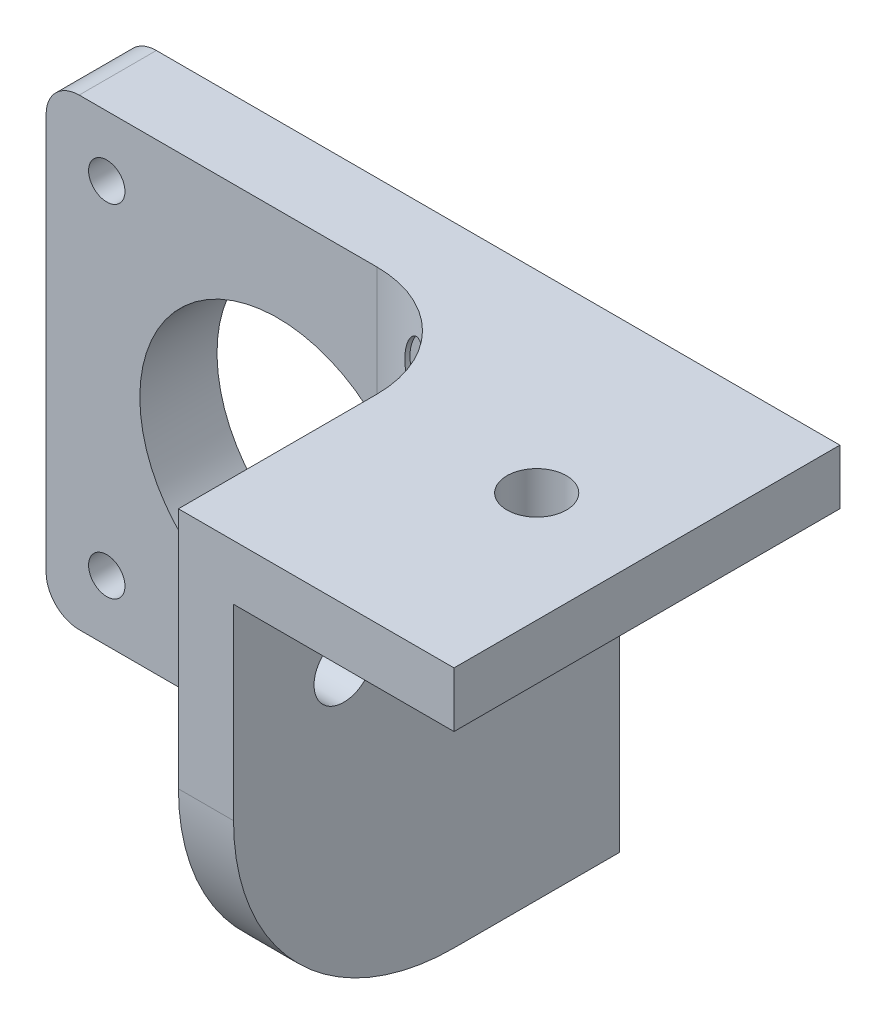
SolidWorks part; units mm, degrees
ref_plane "Front Plane" through (0, 0, 0) normal (0, 0, 1) x (1, 0, 0)
ref_plane "Top Plane" through (0, 0, 0) normal (0, 1, 0) x (1, 0, 0)
ref_plane "Right Plane" through (0, 0, 0) normal (1, 0, 0) x (0, 0, -1)
sketch "Sketch1" plane through (0, 0, 0) normal (0, 0, 1) x (1, 0, 0)
  line L1 (-21, -21) -> (21, -21)
  line L2 (-21, -21) -> (-21, 21)
  line L3 (-21, 21) -> (21, 21)
  line L4 (21, -21) -> (21, 21)
  line L5 (-21, -21) -> (21, 21) construction
  line L6 (-21, 21) -> (21, -21) construction
  point P0 (0, 0)
  dimension "D1" = 42
  dimension "D2" = 42
extrude "Boss-Extrude1" add sketch "Sketch1" along normal blind 7
sketch "Sketch2" plane through (0, 0, 0) normal (0, 0, 1) x (1, 0, 0)
  line L0 (-21, -21) -> (21, -21) construction
  line L1 (19, -21) -> (24, -21)
  line L2 (19, -21) -> (19, 21)
  line L3 (19, 21) -> (24, 21)
  line L4 (24, -21) -> (24, 21)
  line L5 (21, -21) -> (21, 21) construction
  line L6 (21, 21) -> (-21, 21) construction
  dimension "D1" = 3
  dimension "D2" = 5
extrude "Boss-Extrude2" add sketch "Sketch2" along normal blind 35 contours L4 L3 L2 L1
sketch "Sketch3" plane through (0, 0, 7) normal (0, 0, 1) x (1, 0, 0)
  line L1 (-15.5, -15.5) -> (15.5, -15.5) construction
  line L2 (-15.5, -15.5) -> (-15.5, 15.5) construction
  line L3 (-15.5, 15.5) -> (15.5, 15.5) construction
  line L4 (15.5, -15.5) -> (15.5, 15.5) construction
  line L5 (-15.5, -15.5) -> (15.5, 15.5) construction
  line L6 (-15.5, 15.5) -> (15.5, -15.5) construction
  circle A8 centre (-15.5, 15.5) radius 1.65
  circle A9 centre (15.5, 15.5) radius 1.65
  circle A10 centre (15.5, -15.5) radius 1.65
  circle A11 centre (-15.5, -15.5) radius 1.65
  point P0 (0, 0)
  dimension "D1" = 31
  dimension "D2" = 31
  dimension "D3" = 3.3
extrude "Cut-Extrude1" cut sketch "Sketch3" against normal blind 35
sketch "Sketch4" plane through (24, 0, 0) normal (1, 0, 0) x (0, 0, -1)
  line L0 (-35, -21) -> (-35, 21) construction
  line L1 (0, 21) -> (-35, 21)
  line L2 (0, 21) -> (0, 16)
  line L3 (0, 16) -> (-35, 16)
  line L4 (-35, 21) -> (-35, 16)
  dimension "D1" = 5
extrude "Boss-Extrude3" add sketch "Sketch4" along normal blind 20
sketch "Sketch6" plane through (0, 0, 0) normal (0, 0, 1) x (1, 0, 0)
  circle A0 centre (0, 0) radius 12.5
  dimension "D1" = 25
extrude "Cut-Extrude4" cut sketch "Sketch6" along normal blind 20
fillet "Fillet2" radius 10 1 edges at (19, 0, 7)
sketch "Sketch7" plane through (0, 0, 7) normal (0, 0, 1) x (1, 0, 0)
  circle A0 centre (15.5, 15.5) radius 3.5
  circle A1 centre (15.5, -15.5) radius 3.5
  dimension "D1" = 7
extrude "Cut-Extrude5" cut sketch "Sketch7" along normal blind 20
sketch "Sketch11" plane through (24, 0, 0) normal (1, 0, 0) x (0, 0, -1)
  line L0 (-35, 16) -> (0, 16) construction
  line L1 (-35, -21) -> (-35, 16) construction
  circle A0 centre (-25, 6) radius 2.7
  dimension "D3" = 5.4
  dimension "D1" = 10
  dimension "D2" = 10
extrude "Cut-Extrude9" cut sketch "Sketch11" against normal blind 10
sketch "Sketch10" plane through (0, 21, 0) normal (0, 1, 0) x (1, 0, 0)
  line L0 (44, 0) -> (44, -35) construction
  line L1 (44, -17.5) -> (26.4491, -17.5) construction
  circle A0 centre (34, -17.5) radius 2.7
  dimension "D1" = 5.4
  dimension "D2" = 10
extrude "Cut-Extrude8" cut sketch "Sketch10" against normal blind 20 contours A0
fillet "Fillet3" radius 3 2 edges at (-21, -21, 3.5) (-21, 21, 3.5)
fillet "Fillet4" radius 20 1 edges at (21.5, -21, 35)
